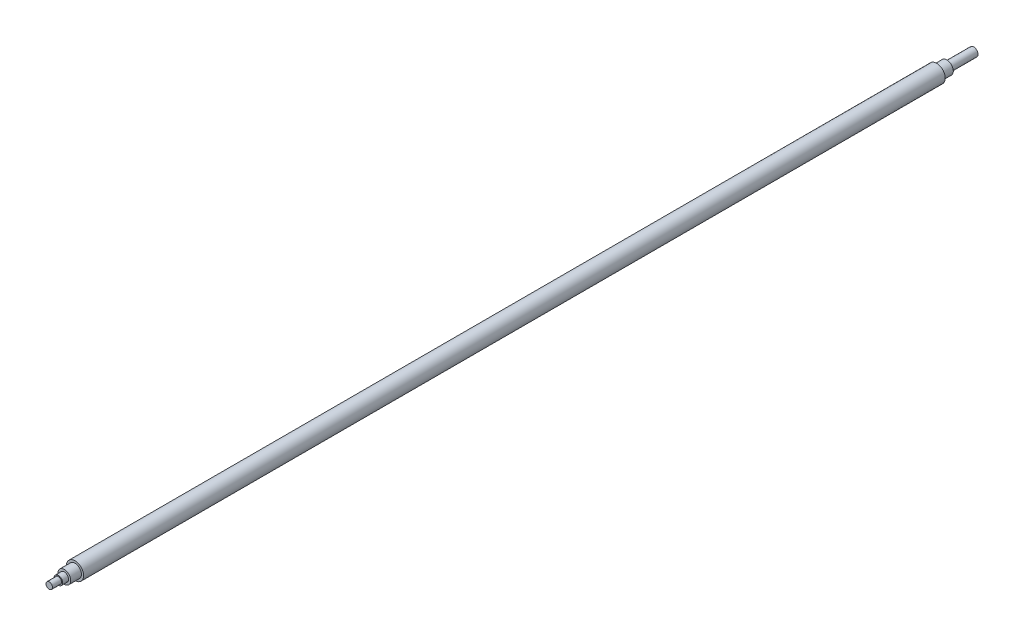
SolidWorks part; units mm, degrees
ref_plane "Piano frontale" through (0, 0, 0) normal (0, 0, 1) x (1, 0, 0)
ref_plane "Piano superiore" through (0, 0, 0) normal (0, 1, 0) x (1, 0, 0)
ref_plane "Piano destro" through (0, 0, 0) normal (1, 0, 0) x (0, 0, -1)
sketch "Schizzo2" plane through (0, 0, 0) normal (1, 0, 0) x (0, 0, -1)
  line L0 (0, 0) -> (0, 3)
  line L1 (0, 3) -> (8.5, 3)
  line L2 (8.5, 3) -> (8.5, 4)
  line L3 (8.5, 4) -> (14, 4)
  line L4 (14, 4) -> (14, 6)
  line L5 (14, 6) -> (24, 6)
  line L6 (24, 6) -> (24, 8)
  line L7 (24, 8) -> (826, 8)
  line L8 (826, 8) -> (826, 6)
  line L9 (826, 6) -> (835.5, 6)
  line L10 (835.5, 6) -> (835.5, 4)
  line L11 (860.5, 0) -> (0, 0)
  line L14 (860.5, 0) -> (860.5, 4)
  line L15 (0, 0) -> (351.0218, 0) construction
  line L18 (835.5, 4) -> (860.5, 4)
  point P33 (0, 0)
  dimension "D2" = 6
  dimension "D3" = 8
  dimension "D4" = 12
  dimension "D5" = 16
  dimension "D6" = 12
  dimension "D7" = 8
  dimension "D8" = 8.5
  dimension "D9" = 5.5
  dimension "D10" = 10
  dimension "D11" = 802
  dimension "D12" = 9.5
  dimension "D13" = 25
revolve "Rivoluzione2" add sketch "Schizzo2" angle 360 about L15
